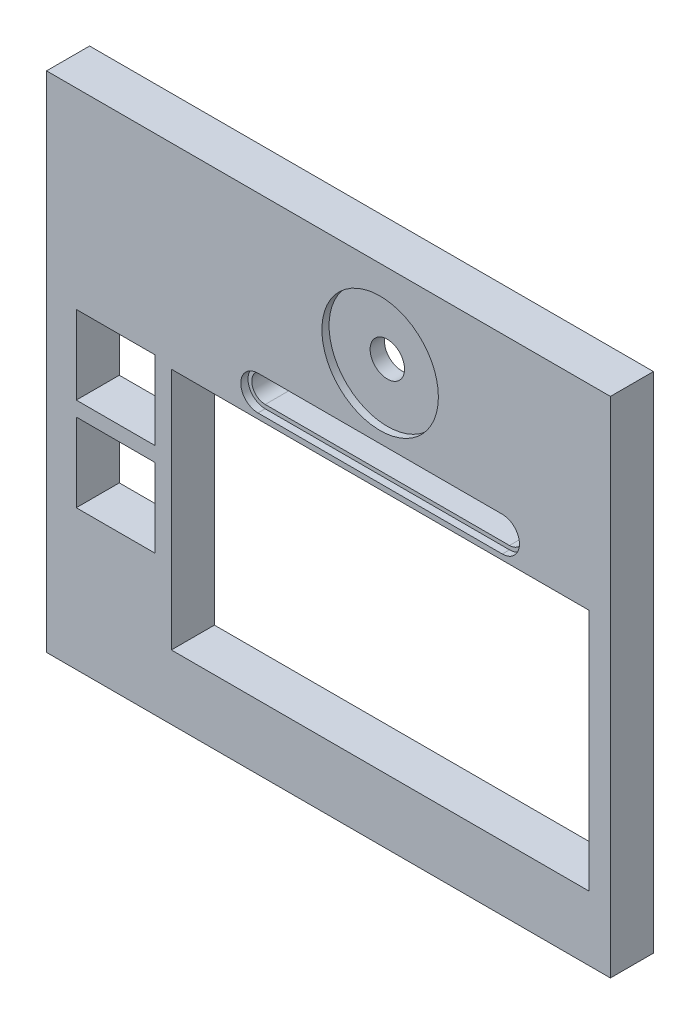
SolidWorks part; units mm, degrees
ref_plane "Front Plane" through (0, 0, 0) normal (0, 0, 1) x (1, 0, 0)
ref_plane "Top Plane" through (0, 0, 0) normal (0, 1, 0) x (1, 0, 0)
ref_plane "Right Plane" through (0, 0, 0) normal (1, 0, 0) x (0, 0, -1)
sketch "Sketch1" plane through (0, 0, 0) normal (0, 0, 1) x (1, 0, 0)
  line L0 (2.9306, 114.5004) -> (112.7856, 114.5004) construction
  line L2 (29.464, 72.644) -> (128.016, 72.644)
  line L3 (29.464, 72.644) -> (29.464, 15.24)
  line L4 (29.464, 15.24) -> (128.016, 15.24)
  line L5 (128.016, 72.644) -> (128.016, 15.24)
  line L6 (78.74, 1.392) -> (78.74, 118.8901) construction
  line L7 (7.0189, 51.6333) -> (25.5609, 51.6333)
  line L8 (7.0189, 51.6333) -> (7.0189, 33.0913)
  line L9 (7.0189, 33.0913) -> (25.5609, 33.0913)
  line L11 (7.0189, 73.639) -> (25.5609, 73.639)
  line L12 (7.0189, 73.639) -> (7.0189, 55.097)
  line L13 (7.0189, 55.097) -> (25.5609, 55.097)
  line L14 (25.5609, 73.639) -> (25.5609, 55.097)
  line L15 (7.0189, 73.639) -> (25.5609, 55.097) construction
  line L16 (7.0189, 55.097) -> (25.5609, 73.639) construction
  line L20 (49.911, 77.978) -> (107.569, 77.978) construction
  line L21 (49.911, 81.153) -> (107.569, 81.153)
  line L22 (49.911, 74.803) -> (107.569, 74.803)
  line L23 (49.911, 77.978) -> (107.569, 77.978) construction
  line L24 (49.911, 82.042) -> (107.569, 82.042)
  line L25 (49.911, 73.914) -> (107.569, 73.914)
  line L26 (25.5609, 51.6333) -> (25.5609, 33.0913)
  line L31 (7.0189, 51.6333) -> (25.5609, 33.0913) construction
  line L32 (0, 0) -> (133.096, 0)
  line L37 (0, 0) -> (0, 118.8901)
  line L38 (0, 118.8901) -> (133.096, 118.8901)
  line L39 (133.096, 0) -> (133.096, 118.8901)
  line L40 (7.0189, 33.0913) -> (25.5609, 51.6333) construction
  arc A1 (49.911, 81.153) -> (49.911, 74.803) centre (49.911, 77.978) ccw
  arc A2 (107.569, 74.803) -> (107.569, 81.153) centre (107.569, 77.978) ccw
  arc A3 (49.911, 82.042) -> (49.911, 73.914) centre (49.911, 77.978) ccw
  arc A4 (107.569, 73.914) -> (107.569, 82.042) centre (107.569, 77.978) ccw
  circle A10 centre (78.74, 98.4758) radius 4.064
  circle A12 centre (78.74, 98.4758) radius 13.75
  circle A13 centre (78.74, 98.4758) radius 7.5
  point P0 (16.2899, 42.3623)
  point P11 (78.74, 15.24)
  point P20 (16.2899, 64.368)
  point P28 (78.74, 77.978)
  point P35 (78.74, 77.978)
  dimension "D7" = 3.175
  dimension "D8" = 1.27
  dimension "D14" = 4.064
  dimension "D17" = 8.128
  dimension "D23" = 57.658
  dimension "D28" = 27.5
  dimension "D31" = 15
  dimension "D2" = 98.552
  dimension "D3" = 57.404
  dimension "D4" = 109.855
  dimension "D5" = 18.542
  dimension "D6" = 18.542
  dimension "D9" = 18.542
  dimension "D10" = 18.542
  dimension "D11" = 5.08
  dimension "D12" = 15.24
  dimension "D13" = 46.2461
  dimension "D15" = 29.464
  dimension "D16" = 17.8513
  dimension "D18" = 7.0189
  dimension "D19" = 3.4637
  dimension "D20" = 7.0189
  dimension "D21" = 25.8318
extrude "Boss-Extrude1" add sketch "Sketch1" against normal blind 10.16 contours L32 L39 L38 L37
extrude "Cut-Extrude1" cut sketch "Sketch1<11>" against normal through all contours L5 L2 L3 L4 | A10 | L14 L11 L12 L13 | L26 L7 L8 L9 | L22 A2 L21 A1 region at (78.74, 43.942, 0) region at (16.2899, 42.3623, 0) region at (16.2899, 64.368, 0) region at (78.74, 77.978, 0) region at (78.74, 98.4758, 0)
sketch "Sketch1<11>" plane through (0, 0, 0) normal (0, 0, 1) x (1, 0, 0) same geometry as "Sketch1"
extrude "Cut-Extrude2" cut sketch "Sketch1<12>" against normal blind 1.7 contours A12 A13 | A13 A10 | L25 A4 L24 A3 A2 L22 A1 L21 region at (78.74, 81.3791, 0) region at (65.3789, 98.4758, 0) region at (71.4521, 98.4758, 0)
sketch "Sketch1<12>" plane through (0, 0, 0) normal (0, 0, 1) x (1, 0, 0) same geometry as "Sketch1"
sketch "Sketch2" plane through (0, 0, 0) normal (0, 0, 1) x (1, 0, 0)
  line L0 (14.5561, 105.4962) -> (124.4111, 105.4962) construction
  dimension "D1" = 109.855
ref_plane "Plane1" through (0, 0, -12.7) normal (0, 0, -1) x (-1, 0, 0)
sketch "Sketch3" plane through (0, 0, -12.7) normal (0, 0, -1) x (-1, 0, 0)
  line L0 (-112.6914, 114.4545) -> (-2.8364, 114.4545) construction
  dimension "D1" = 109.855
hole_wizard "CSK for M2.5 Flat Head Machine Screw1" positions "Sketch4" profile "Sketch5" countersink size "M2.5" standard "ANSI Metric"
sketch "Sketch4" plane through (0, 0, -10.16) normal (0, 0, -1) x (-1, 0, 0)
  point P0 (-109.2504, 110.9328)
  point P2 (-65.0894, 110.9328)
  point P4 (-6.4749, 110.9328)
  point P6 (-16.1769, 29.2174)
sketch "Sketch5" plane through (109.2504, 110.9328, -10.16) normal (1, 0, 0) x (0, 1, 0)
  line L0 (0, 0) -> (0, 5.9512)
  line L1 (0, 5.9512) -> (1.45, 5.08)
  line L2 (1.45, 5.08) -> (1.45, 1.3)
  line L3 (1.45, 1.3) -> (2.75, 0)
  line L5 (2.75, 0) -> (0, 0)
  line L6 (-1.45, 1.3) -> (-2.75, 0) construction
  line L10 (0, 5.9512) -> (-1.45, 5.08) construction
  line L11 (0, -6.35) -> (0, 107.95) construction
  dimension "Hole Dia." = 2.9
  dimension "Hole Depth" = 5.08
  dimension "Near C'Sink Dia." = 5.5
  dimension "Near C'Sink Angle" = 90
  dimension "Drill Angle" = 118
sketch "Sketch6" plane through (0, 0, -12.7) normal (0, 0, -1) x (-1, 0, 0)
  line L0 (-130.556, 116.3501) -> (-2.54, 116.3501)
  line L1 (-133.096, 0) -> (-133.096, 118.8901) construction
  line L2 (0, 118.8901) -> (-133.096, 118.8901) construction
  line L3 (0, 0) -> (0, 118.8901) construction
  line L4 (-130.556, 116.3501) -> (-130.556, 75.184)
  line L5 (-29.464, 72.644) -> (-128.016, 72.644) construction
  line L6 (-2.54, 116.3501) -> (-2.54, 111.7553)
  line L7 (-107.569, 77.978) -> (-49.911, 77.978) construction
  line L8 (-107.569, 82.423) -> (-49.911, 82.423)
  line L10 (-49.911, 81.153) -> (-107.569, 81.153) construction
  line L11 (-130.556, 75.184) -> (-111.0261, 75.184)
  line L12 (-2.54, 75.184) -> (-46.4539, 75.184)
  line L13 (-2.54, 110.1102) -> (-2.54, 75.184)
  line L14 (-26.924, 30.5513) -> (-26.924, 2.54)
  line L15 (-26.924, 2.54) -> (-2.54, 2.54)
  line L16 (-2.54, 2.54) -> (-2.54, 30.5513)
  line L17 (-2.54, 30.5513) -> (-12.3846, 30.5513)
  line L18 (-26.924, 30.5513) -> (-19.9691, 30.5513)
  line L19 (-7.0189, 33.0913) -> (-25.5609, 33.0913) construction
  line L20 (0, 0) -> (-133.096, 0) construction
  line L21 (-29.464, 72.644) -> (-29.464, 15.24) construction
  circle A0 centre (-109.2504, 110.9328) radius 4.02
  circle A1 centre (-65.0894, 110.9328) radius 4.02
  arc A2 (-2.54, 111.7553) -> (-2.54, 110.1102) centre (-6.4749, 110.9328) ccw
  arc A3 (-19.9691, 30.5513) -> (-12.3846, 30.5513) centre (-16.1769, 29.2174) ccw
  circle A4 centre (-109.2504, 110.9328) radius 2.75 construction
  circle A5 centre (-65.0894, 110.9328) radius 2.75 construction
  circle A6 centre (-6.4749, 110.9328) radius 2.75 construction
  circle A7 centre (-16.1769, 29.2174) radius 2.75 construction
  arc A8 (-107.569, 82.423) -> (-111.0261, 75.184) centre (-107.569, 77.978) ccw
  arc A9 (-46.4539, 75.184) -> (-49.911, 82.423) centre (-49.911, 77.978) ccw
  point P36 (-78.74, 77.978)
  dimension "D1" = 1.27
  dimension "D2" = 1.27
  dimension "D3" = 1.27
  dimension "D4" = 1.27
  dimension "D10" = 4.445
  dimension "D11" = 4.445
  dimension "D5" = 2.54
  dimension "D6" = 2.54
  dimension "D7" = 2.54
  dimension "D8" = 2.54
  dimension "D9" = 1.27
  dimension "D12" = 2.54
  dimension "D13" = 2.54
  dimension "D14" = 2.54
  dimension "D15" = 2.54
  dimension "D16" = 2.54
  dimension "D17" = 2.54
extrude "Cut-Extrude3" cut sketch "Sketch6" against normal blind 7.62
